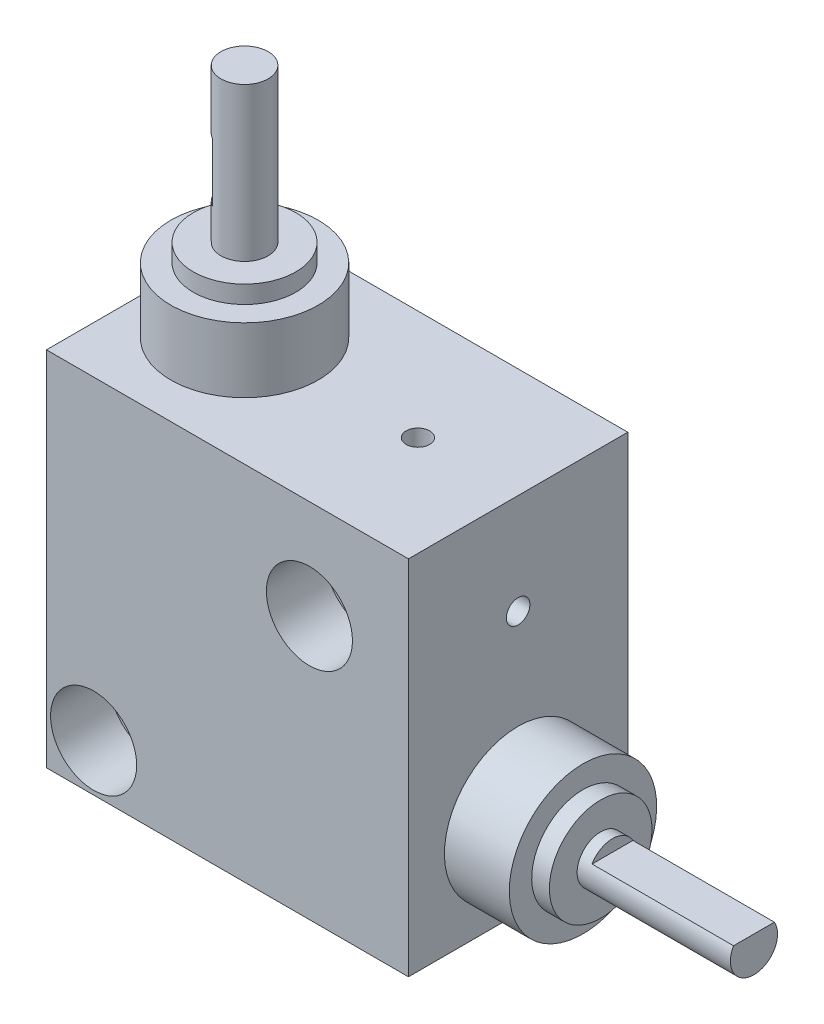
SolidWorks part; units mm, degrees
ref_plane "Plan de face" through (0, 0, 0) normal (0, 0, 1) x (1, 0, 0)
ref_plane "Plan de dessus" through (0, 0, 0) normal (0, 1, 0) x (1, 0, 0)
ref_plane "Plan de droite" through (0, 0, 0) normal (1, 0, 0) x (0, 0, -1)
sketch "Esquisse1" plane through (0, 0, 0) normal (0, 0, 1) x (1, 0, 0)
  line L1 (0, 0) -> (30.7, 0)
  line L2 (0, 0) -> (0, 30.7)
  line L3 (0, 30.7) -> (30.7, 30.7)
  line L4 (30.7, 0) -> (30.7, 30.7)
  dimension "D1" = 30.7
  dimension "D2" = 30.7
extrude "Boss.-Extru.1" add sketch "Esquisse1" along normal mid plane 18.6
sketch "Esquisse2" plane through (0, 0, 9.3) normal (0, 0, 1) x (1, 0, 0)
  line L0 (0, 0) -> (30.7, 0) construction
  line L1 (0, 30.7) -> (0, 0) construction
  line L2 (30.7, 0) -> (30.7, 30.7) construction
  line L3 (30.7, 30.7) -> (0, 30.7) construction
  circle A0 centre (4, 4) radius 2
  circle A1 centre (22.3, 22.3) radius 2
  dimension "D1" = 4
  dimension "D4" = 4
  dimension "D2" = 4
  dimension "D3" = 4
  dimension "D5" = 8.4
  dimension "D6" = 8.4
extrude "Enlèv. mat.-Extru.1" cut sketch "Esquisse2" against normal through all
sketch "Esquisse3" plane through (0, 0, 9.3) normal (0, 0, 1) x (1, 0, 0)
  circle A0 centre (4, 4) radius 3.65
  circle A1 centre (4, 4) radius 2 construction
  circle A2 centre (22.3, 22.3) radius 3.65
  circle A3 centre (22.3, 22.3) radius 2 construction
  dimension "D1" = 7.3
extrude "Enlèv. mat.-Extru.2" cut sketch "Esquisse3" against normal blind 5
sketch "Esquisse4" plane through (0, 0, -9.3) normal (0, 0, -1) x (-1, 0, 0)
  circle A0 centre (-4, 4) radius 3.65
  circle A1 centre (-22.3, 22.3) radius 3.65
  circle A2 centre (-22.3, 22.3) radius 2 construction
  dimension "D1" = 7.3
  dimension "D2" = 7.3
extrude "Enlèv. mat.-Extru.3" cut sketch "Esquisse4" against normal blind 5
sketch "Esquisse6" plane through (0, 0, 0) normal (0, 0, 1) x (1, 0, 0)
  line L0 (30.7, 13.75) -> (36.2, 13.75)
  line L1 (36.2, 13.75) -> (36.2, 11.85)
  line L2 (36.2, 11.85) -> (37.7, 11.85)
  line L3 (37.7, 11.85) -> (37.7, 9.5)
  line L4 (37.7, 9.5) -> (50.7, 9.5)
  line L5 (50.7, 9.5) -> (50.7, 7.5)
  line L6 (50.7, 7.5) -> (30.7, 7.5)
  line L7 (30.7, 0) -> (30.7, 30.7) construction
  line L8 (30.7, 7.5) -> (30.7, 13.75)
  line L9 (0, 0) -> (30.7, 0) construction
  dimension "D1" = 2
  dimension "D2" = 20
  dimension "D3" = 5.5
  dimension "D4" = 1.5
  dimension "D5" = 6.25
  dimension "D6" = 7.5
  dimension "D7" = 4.35
revolve "Révolution1" add sketch "Esquisse6" angle 360 about L6
sketch "Esquisse8" plane through (0, 0, 0) normal (0, 0, 1) x (1, 0, 0)
  line L0 (1.25, 30.7) -> (1.25, 36.2)
  line L1 (1.25, 36.2) -> (3.15, 36.2)
  line L2 (3.15, 36.2) -> (3.15, 37.7)
  line L3 (3.15, 37.7) -> (5.5, 37.7)
  line L4 (5.5, 37.7) -> (5.5, 50.7)
  line L5 (5.5, 50.7) -> (7.5, 50.7)
  line L6 (7.5, 50.7) -> (7.5, 30.7)
  line L7 (7.5, 30.7) -> (1.25, 30.7)
  line L8 (30.7, 30.7) -> (0, 30.7) construction
  line L9 (0, 30.7) -> (0, 0) construction
  dimension "D1" = 2
  dimension "D2" = 1.5
  dimension "D3" = 5.5
  dimension "D4" = 20
  dimension "D5" = 6.25
  dimension "D6" = 4.35
  dimension "D7" = 7.5
  dimension "D8" = 0
revolve "Révolution2" add sketch "Esquisse8" angle 360 about L6
ref_plane "Plan1" through (0, 45.7, 0) normal (0, 1, 0) x (1, 0, 0)
sketch "Esquisse9" plane through (0, 45.7, 0) normal (0, 1, 0) x (1, 0, 0)
  line L0 (6.5, -2) -> (5.5, -2)
  line L1 (5.5, -2) -> (5.5, 2)
  line L3 (5.5, 2) -> (6.5, 2)
  line L4 (6.5, -2) -> (6.5, 2)
  circle A0 centre (7.5, 0) radius 2 construction
  point P2 (5.5, 0)
  dimension "D1" = 1
  dimension "D2" = 4
extrude "Enlèv. mat.-Extru.4" cut sketch "Esquisse9" against normal blind 5
ref_plane "Plan2" through (50.7, 0, 0) normal (1, 0, 0) x (0, 0, -1)
sketch "Esquisse10" plane through (50.7, 0, 0) normal (1, 0, 0) x (0, 0, -1)
  line L1 (-2, 9.5) -> (2, 9.5)
  line L2 (-2, 9.5) -> (-2, 8.5)
  line L3 (-2, 8.5) -> (2, 8.5)
  line L4 (2, 9.5) -> (2, 8.5)
  circle A0 centre (0, 7.5) radius 2 construction
  point P6 (0, 9.5)
  dimension "D1" = 1
  dimension "D2" = 4
extrude "Enlèv. mat.-Extru.5" cut sketch "Esquisse10" against normal blind 12
sketch "Esquisse11" plane through (30.7, 0, 0) normal (1, 0, 0) x (0, 0, -1)
  line L0 (-9.3, 30.7) -> (9.3, 30.7) construction
  circle A0 centre (0, 22.2) radius 1
  dimension "D1" = 8.5
  dimension "D2" = 2
extrude "Enlèv. mat.-Extru.6" cut sketch "Esquisse11" against normal blind 5
sketch "Esquisse13" plane through (0, 30.7, 0) normal (0, 1, 0) x (1, 0, 0)
  line L0 (30.7, -9.3) -> (30.7, 9.3) construction
  circle A0 centre (22.2, 0) radius 1
  point P4 (30.7, 0)
  dimension "D1" = 2
  dimension "D2" = 8.5
extrude "Enlèv. mat.-Extru.7" cut sketch "Esquisse13" against normal blind 5
